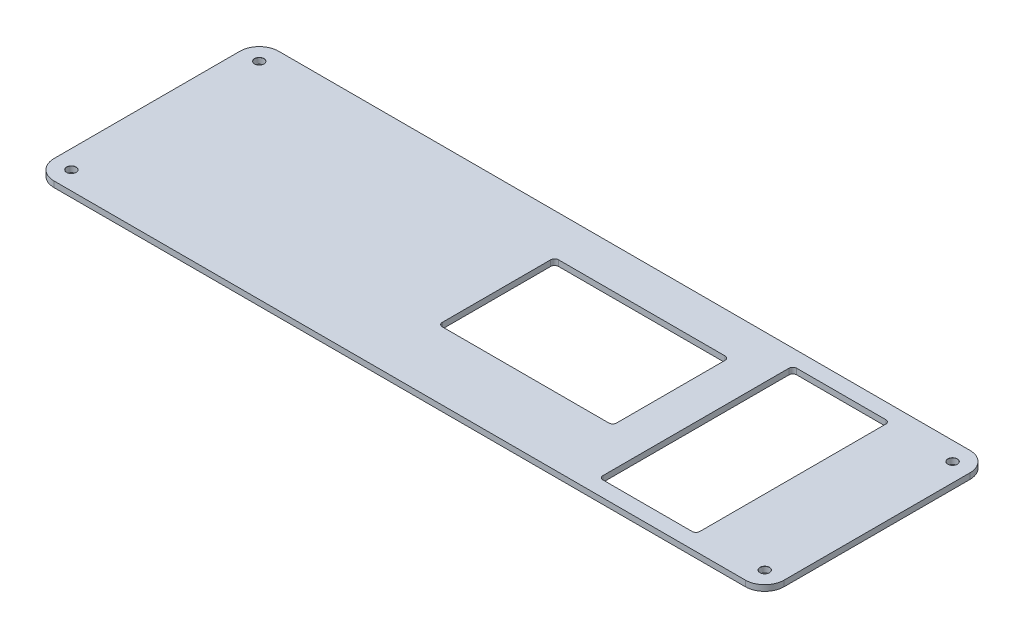
SolidWorks part; units mm, degrees
ref_plane "Front Plane" through (0, 0, 0) normal (0, 0, 1) x (1, 0, 0)
ref_plane "Top Plane" through (0, 0, 0) normal (0, 1, 0) x (1, 0, 0)
ref_plane "Right Plane" through (0, 0, 0) normal (1, 0, 0) x (0, 0, -1)
sketch "Sketch1" plane through (0, 0, 0) normal (0, 1, 0) x (1, 0, 0)
  line L1 (94.25, -29) -> (-94.25, -29)
  line L2 (94.25, -29) -> (94.25, 29)
  line L3 (94.25, 29) -> (-94.25, 29)
  line L4 (-94.25, -29) -> (-94.25, 29)
  line L5 (94.25, -29) -> (-94.25, 29) construction
  line L6 (94.25, 29) -> (-94.25, -29) construction
  point P0 (0, 0)
  dimension "D1" = 58
  dimension "D2" = 188.5
extrude "Boss-Extrude1" add sketch "Sketch1" along normal blind 1.5
fillet "Fillet1" radius 5 4 edges at (-94.25, 0.75, -29) (94.25, 0.75, -29) (94.25, 0.75, 29) (-94.25, 0.75, 29)
hole_wizard "M2 Clearance Hole1" positions "Sketch2" profile "Sketch3" hole size "M2" standard "ANSI Metric" end condition up to next
sketch "Sketch2" plane through (0, 1.5, 0) normal (0, 1, 0) x (1, 0, 0)
  line L0 (-89.5, -24.25) -> (-89.5, 24.25) construction
  line L1 (-89.5, 24.25) -> (89.5, 24.25) construction
  line L2 (89.5, 24.25) -> (-89.5, -24.25) construction
  line L6 (89.5, 24.25) -> (89.5, -24.25) construction
  line L7 (89.5, -24.25) -> (-89.5, -24.25) construction
  point P0 (-89.5, 24.25)
  point P2 (89.5, 24.25)
  point P4 (89.5, -24.25)
  point P6 (-89.5, -24.25)
  point P16 (0, 0)
  dimension "D1" = 179
  dimension "D2" = 48.5
sketch "Sketch3" plane through (-89.5, 1.5, -24.25) normal (1, 0, 0) x (0, 0, 1)
  line L0 (0, 0) -> (0, 1.5)
  line L1 (0, 1.5) -> (1.2, 1.5)
  line L2 (1.2, 1.5) -> (1.2, 0.025)
  line L3 (1.2, 0.025) -> (1.225, 0)
  line L5 (1.225, 0) -> (0, 0)
  line L6 (-1.2, 0.025) -> (-1.225, 0) construction
  line L11 (0, -6.35) -> (0, 107.95) construction
  dimension "Thru Hole Dia." = 2.4
  dimension "Thru Hole Depth" = 1.5
  dimension "Near C'Sink Dia." = 2.45
  dimension "Near C'Sink Angle" = 90
sketch "Sketch4" plane through (0, 1.5, 0) normal (0, 1, 0) x (1, 0, 0)
  line L17 (37.5, -11.5) -> (-7.5, -11.5)
  line L18 (37.5, -11.5) -> (37.5, 18.5)
  line L19 (37.5, 18.5) -> (-7.5, 18.5)
  line L20 (-7.5, -11.5) -> (-7.5, 18.5)
  line L21 (37.5, -11.5) -> (-7.5, 18.5) construction
  line L22 (37.5, 18.5) -> (-7.5, -11.5) construction
  point P0 (15, 3.5)
  dimension "D1" = 15
  dimension "D2" = 45
  dimension "D3" = 30
  dimension "D4" = 3.5
extrude "Cut-Extrude1" cut sketch "Sketch4" against normal through all
sketch "Sketch5" plane through (0, 1.5, 0) normal (0, 1, 0) x (1, 0, 0)
  line L1 (72.5, -25) -> (47.5, -25)
  line L2 (72.5, -25) -> (72.5, 25)
  line L3 (72.5, 25) -> (47.5, 25)
  line L4 (47.5, -25) -> (47.5, 25)
  line L5 (72.5, -25) -> (47.5, 25) construction
  line L6 (72.5, 25) -> (47.5, -25) construction
  point P0 (60, 0)
  point P5 (0, 0)
  dimension "D1" = 25
  dimension "D2" = 50
  dimension "D3" = 60
extrude "Cut-Extrude2" cut sketch "Sketch5" against normal through all
fillet "Fillet2" radius 1 8 edges at (37.5, 0.75, 11.5) (-7.5, 0.75, 11.5) (-7.5, 0.75, -18.5) (37.5, 0.75, -18.5) (72.5, 0.75, 25) (47.5, 0.75, 25) (47.5, 0.75, -25) (72.5, 0.75, -25)
